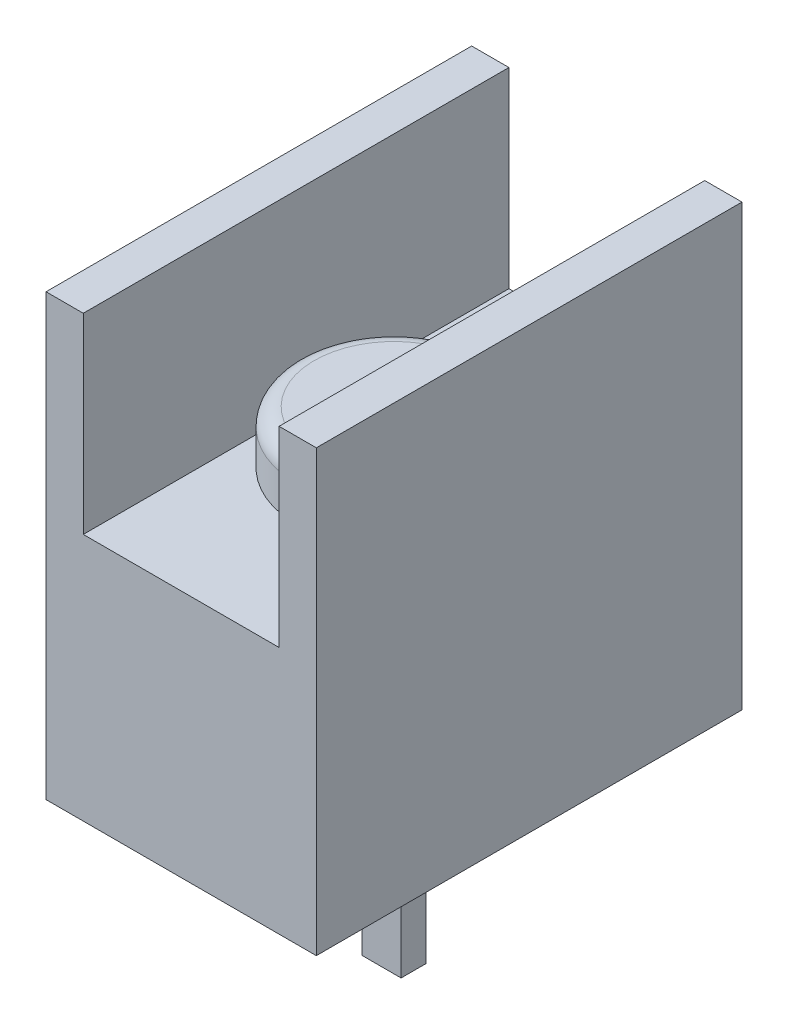
SolidWorks part; units mm, degrees
ref_plane "前视基准面" through (0, 0, 0) normal (0, 0, 1) x (1, 0, 0)
ref_plane "上视基准面" through (0, 0, 0) normal (0, 1, 0) x (1, 0, 0)
ref_plane "右视基准面" through (0, 0, 0) normal (1, 0, 0) x (0, 0, -1)
sketch "草图1" plane through (0, 0, 0) normal (0, 1, 0) x (1, 0, 0)
  line L0 (-11.1447, 0) -> (12.1543, 0) construction
  line L1 (-3.81, 6) -> (3.81, 6)
  line L2 (-3.81, 6) -> (-3.81, -6)
  line L3 (-3.81, -6) -> (3.81, -6)
  line L4 (3.81, 6) -> (3.81, -6)
  line L5 (0, 11.4931) -> (0, -8.9219) construction
  dimension "D1" = 7.62
  dimension "D2" = 12
extrude "拉伸1" add sketch "草图1" along normal blind 12.4
sketch "草图2" plane through (0, 12.4, 0) normal (0, 1, 0) x (-1, 0, 0)
  line L0 (3.81, 6) -> (-3.81, 6) construction
  line L1 (-2.76, 6) -> (2.76, 6)
  line L3 (-2.76, 6) -> (-2.76, -6)
  line L4 (-2.76, -6) -> (2.76, -6)
  line L5 (2.76, 6) -> (2.76, -6)
  line L6 (-3.81, -6) -> (3.81, -6) construction
  line L7 (-3.81, 6) -> (-3.81, -6) construction
  line L10 (3.81, -6) -> (3.81, 6) construction
  dimension "D1" = 1.05
  dimension "D2" = 1.05
extrude "切除-拉伸1" cut sketch "草图2" against normal offset from surface (5.4 mm away) 7 up to face at (0, 0, 0)
sketch "草图3" plane through (0, 0, 0) normal (0, -1, 0) x (1, 0, 0)
  line L0 (-1.1261, 0) -> (1.1036, 0) construction
  line L1 (-0.55, 0.35) -> (0.55, 0.35)
  line L2 (-0.55, 0.35) -> (-0.55, -0.35)
  line L3 (-0.55, -0.35) -> (0.55, -0.35)
  line L4 (0.55, 0.35) -> (0.55, -0.35)
  line L5 (0, 0.8666) -> (0, -0.8367) construction
  dimension "D2" = 0.7
  dimension "D1" = 1.1
extrude "拉伸2" add sketch "草图3" along normal blind 5
sketch "草图4" plane through (0, 7, 0) normal (0, 1, 0) x (-1, 0, 0)
  line L0 (-9.5136, 0) -> (8.6579, 0) construction
  line L1 (0, -7.7686) -> (0, 8.3952) construction
  circle A1 centre (0, 0) radius 2.75
  dimension "D1" = 5.5
extrude "凸台-拉伸1" add sketch "草图4" along normal blind 1.5
fillet "圆角1" radius 0.5 1 edges at (0, 8.5, -2.75)
